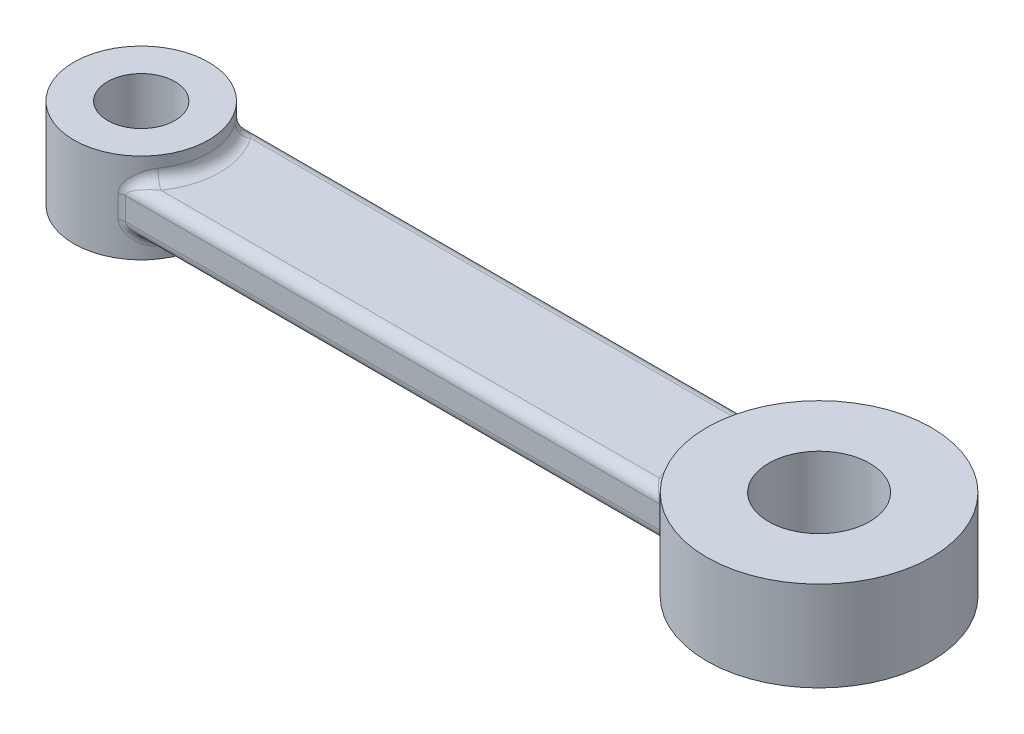
SolidWorks part; units mm, degrees
ref_plane "Front Plane" through (0, 0, 0) normal (0, 0, 1) x (1, 0, 0)
ref_plane "Top Plane" through (0, 0, 0) normal (0, 1, 0) x (1, 0, 0)
ref_plane "Right Plane" through (0, 0, 0) normal (1, 0, 0) x (0, 0, -1)
sketch "Sketch1" plane through (0, 0, 0) normal (0, 0, 1) x (1, 0, 0)
  line L1 (-15, -1) -> (15, -1)
  line L2 (-15, -1) -> (-15, 1)
  line L3 (-15, 1) -> (15, 1)
  line L4 (15, -1) -> (15, 1)
  line L5 (-15, -1) -> (15, 1) construction
  line L6 (-15, 1) -> (15, -1) construction
  point P0 (0, 0)
  dimension "D1" = 2
  dimension "D2" = 30
extrude "Boss-Extrude1" add sketch "Sketch1" along normal mid plane 5
sketch "Sketch3" plane through (0, 0, 0) normal (0, 1, 0) x (1, 0, 0)
  line L0 (-16.6651, 0) -> (18.4359, 0) construction
  line L1 (-15, -2.5) -> (-15, 2.5) construction
  circle A0 centre (15.0086, 0) radius 5
  circle A1 centre (-15.153, 0) radius 3
  point P7 (0, 0)
  point P10 (-15, 0)
  point P11 (0.8854, 0)
  dimension "D1" = 10
  dimension "D2" = 6
extrude "Boss-Extrude3" add sketch "Sketch3" along normal mid plane 4
sketch "Sketch4" plane through (0, 2, 0) normal (0, 1, 0) x (1, 0, 0)
  line L0 (-21.7257, 0) -> (27.1033, 0) construction
  circle A0 centre (-15.153, 0) radius 1.5
  circle A1 centre (15.0086, 0) radius 2.25
  dimension "D1" = 3
  dimension "D2" = 4.5
extrude "Cut-Extrude1" cut sketch "Sketch4" against normal through all
fillet "Fillet1" radius 0.5 4 edges at (-1.4081, -1, -2.5) (-1.4081, 1, -2.5) (-1.4081, -1, 2.5) (-1.4081, 1, 2.5)
fillet "Fillet2" radius 0.5 16 edges at (-13.4293, 0.7066, 2.4553) (-13.4947, 0, 2.5) (-13.3511, -0.8019, 2.3986) (-12.153, -1, 0) (-13.4293, -0.7066, -2.4553) (-13.4947, 0, -2.5) (-13.3511, 0.8019, -2.3986) (10.629, 0.7829, -2.4123) (10.6784, 0, -2.5) (10.5887, -0.8688, -2.3376) (10.0086, -1, 0) (10.629, -0.7829, 2.4123) (10.6784, 0, 2.5) (10.5887, 0.8688, 2.3376) (-12.153, 1, 0) (10.0086, 1, 0)
